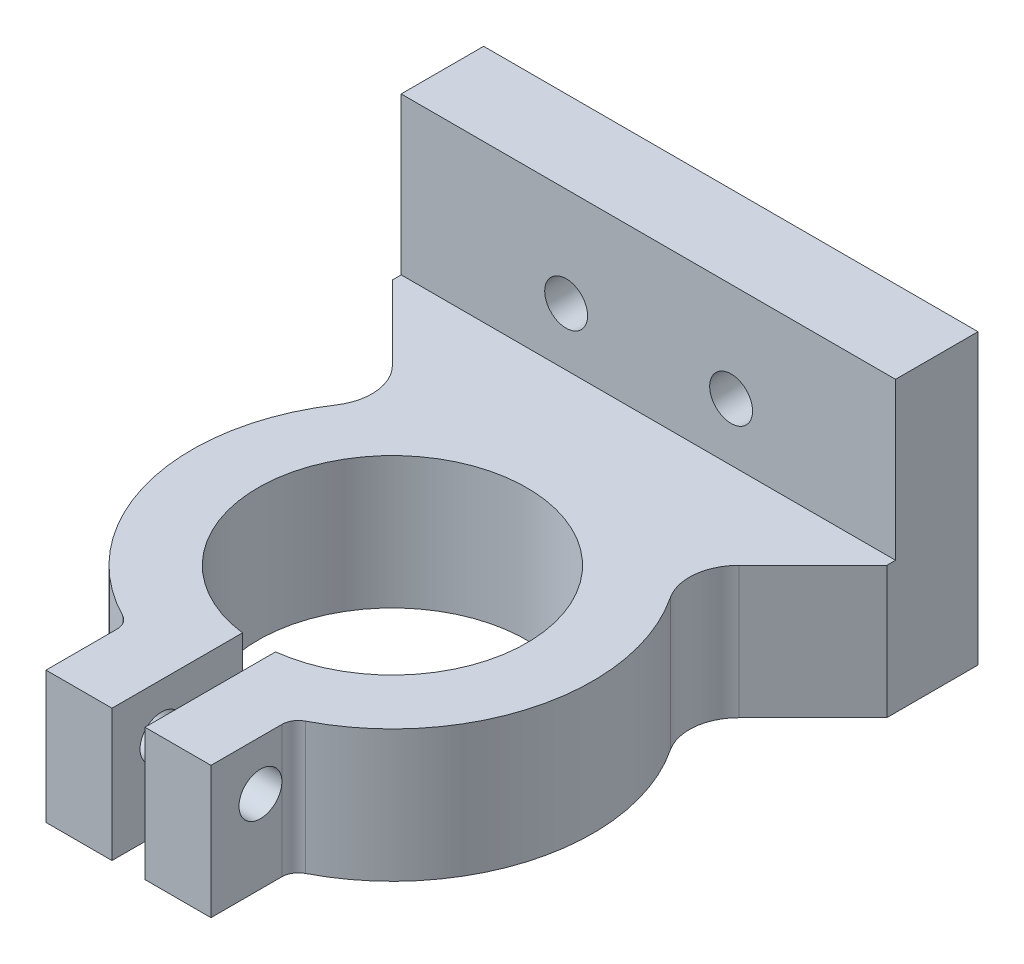
SolidWorks part; units mm, degrees
ref_plane "Front Plane" through (0, 0, 0) normal (0, 0, 1) x (1, 0, 0)
ref_plane "Top Plane" through (0, 0, 0) normal (0, 1, 0) x (1, 0, 0)
ref_plane "Right Plane" through (0, 0, 0) normal (1, 0, 0) x (0, 0, -1)
sketch "Sketch1" plane through (0, 0, 0) normal (0, 1, 0) x (1, 0, 0)
  line L0 (-28.2843, 0) -> (0, 28.2843) construction
  line L1 (-28.2843, 0) -> (0, -28.2843) construction
  line L2 (0, 28.2843) -> (28.2843, 0) construction
  line L3 (0, -28.2843) -> (28.2843, 0) construction
  line L4 (-28.2843, 0) -> (28.2843, 0) construction
  line L5 (0, 28.2843) -> (0, -28.2843) construction
  line L6 (-28.6378, -0.3536) -> (0, -28.9914)
  line L7 (0, -28.9914) -> (28.6378, -0.3536)
  point P1 (0, 0)
  dimension "D1" = 40
  dimension "D2" = 0.5
extrude "Extrude-Thin1" add sketch "Sketch1" along normal blind 60 thin contours L6 L7 thin type one direction wall 4
sketch "Sketch2" plane through (0, 0, 0) normal (0, 1, 0) x (1, 0, 0)
  line L0 (-31.4663, -3.182) -> (-31.4663, -85)
  line L1 (-31.4663, -85) -> (-2, -85)
  line L2 (31.4663, -85) -> (31.4663, -3.182)
  line L3 (-31.4663, -3.182) -> (0, -34.6482) construction
  line L4 (0, -34.6482) -> (31.4663, -3.182) construction
  line L5 (-31.4663, -3.182) -> (0, -34.6482)
  line L6 (0, -34.6482) -> (31.4663, -3.182)
  line L7 (0, -70) -> (0, -77.0884) construction
  line L8 (-2, -69.1768) -> (-2, -85)
  line L9 (0, -53) -> (0, -34.6482) construction
  line L11 (2, -69.1768) -> (2, -85)
  line L12 (-2, -69.1768) -> (2, -85) construction
  line L13 (-2, -85) -> (2, -69.1768) construction
  line L14 (2, -85) -> (31.4663, -85)
  arc A1 (2, -69.1768) -> (-2, -69.1768) centre (0, -53) ccw
  dimension "D4" = 16.3
  dimension "D1" = 85
  dimension "D2" = 4
  dimension "D3" = 32
extrude "Boss-Extrude1" add sketch "Sketch2" along normal blind 16
sketch "Sketch3" plane through (17.3241, 0, 17.3241) normal (0.7071, 0, 0.7071) x (0.7071, 0, -0.7071)
  line L0 (0, 50) -> (0, 20) construction
  line L1 (2.75, 50) -> (2.75, 20)
  line L2 (-2.75, 50) -> (-2.75, 20)
  arc A0 (2.75, 50) -> (-2.75, 50) centre (0, 50) ccw
  arc A1 (-2.75, 20) -> (2.75, 20) centre (0, 20) ccw
  point P3 (0, 35)
  dimension "D3" = 2.75
  dimension "D1" = 20
  dimension "D2" = 30
extrude "Cut-Extrude1" cut sketch "Sketch3" against normal through all
mirror "Mirror1" about plane through (0, 0, 0) normal (1, 0, 0) of "Cut-Extrude1"
sketch "Sketch5" plane through (0, 0, 0) normal (0, 1, 0) x (1, 0, 0)
  line L0 (-31.4663, -21.5337) -> (-17.1827, -35.8173)
  line L1 (-31.4663, -3.182) -> (-31.4663, -85) construction
  line L2 (-10, -75.147) -> (-10, -85)
  line L3 (-31.4663, -85) -> (-2, -85) construction
  line L4 (-31.4663, -3.182) -> (0, -34.6482) construction
  line L5 (-2, -85) -> (-2, -69.1768) construction
  line L6 (-10, -85) -> (-31.4663, -85)
  line L7 (-31.4663, -85) -> (-31.4663, -21.5337)
  arc A0 (-17.1827, -35.8173) -> (-10, -75.147) centre (0, -53) ccw
  arc A1 (2, -69.1768) -> (-2, -69.1768) centre (0, -53) ccw construction
  dimension "D1" = 8
  dimension "D2" = 8
extrude "Cut-Extrude2" cut sketch "Sketch5" along normal through all
mirror "Mirror2" about plane through (0, 0, 0) normal (1, 0, 0) of "Cut-Extrude2"
fillet "Fillet2" radius 2 2 edges at (10, 8, 75.147) (-10, 8, 75.147)
sketch "Sketch6" plane through (0, 0, 0) normal (1, 0, 0) x (0, 0, -1)
  line L0 (-85, 16) -> (-85, 0) construction
  circle A0 centre (-79, 10) radius 2.6
  dimension "D3" = 5.2
  dimension "D1" = 10
  dimension "D2" = 6
extrude "Cut-Extrude3" cut sketch "Sketch6" against normal through all both and the other way through all
sketch "Sketch7" plane through (-17.3241, 0, 17.3241) normal (-0.7071, 0, 0.7071) x (0.7071, 0, 0.7071)
  line L0 (24.5, 16) -> (-20, 16) construction
  line L1 (-40.1042, 68.8024) -> (38.3195, 68.8024)
  line L2 (-40.1042, 68.8024) -> (-40.1042, 16)
  line L3 (-40.1042, 16) -> (38.3195, 16)
  line L4 (38.3195, 68.8024) -> (38.3195, 16)
  dimension "D1" = 0
extrude "Cut-Extrude4" cut sketch "Sketch7" against normal through all and the other way through all
sketch "Sketch8" plane through (0, 16, 0) normal (0, 1, 0) x (1, 0, 0)
  line L1 (-25.3301, 9.3905) -> (25.9897, 9.3905)
  line L2 (-25.3301, 9.3905) -> (-25.3301, -30.6607)
  line L3 (-25.3301, -30.6607) -> (25.9897, -30.6607)
  line L4 (25.9897, 9.3905) -> (25.9897, -30.6607)
extrude "Boss-Extrude2" add sketch "Sketch8" against normal blind 16
sketch "Sketch9" plane through (0, 16, 0) normal (0, 1, 0) x (1, 0, 0)
  line L1 (-45.4357, 11.8389) -> (46.3414, 11.8389)
  line L2 (-45.4357, 11.8389) -> (-45.4357, -21.9738)
  line L3 (-45.4357, -21.9738) -> (46.3414, -21.9738)
  line L4 (46.3414, 11.8389) -> (46.3414, -21.9738)
extrude "Cut-Extrude5" cut sketch "Sketch9" against normal through all contours L2 L3 L4 L1
sketch "Sketch12" plane through (0, 0, 21.9738) normal (0, 0, -1) x (-1, 0, 0)
  line L1 (-31.4663, 35) -> (31.4663, 35)
  line L2 (-31.4663, 35) -> (-31.4663, 0)
  line L3 (-31.4663, 0) -> (31.4663, 0)
  line L4 (31.4663, 35) -> (31.4663, 0)
  line L5 (31.0262, 16) -> (-31.0262, 16) construction
  circle A0 centre (-10.0337, 23) radius 2.6
  circle A1 centre (9.9663, 23) radius 2.6
  dimension "D2" = 5.2
  dimension "D1" = 35
  dimension "D3" = 20
  dimension "D4" = 21.5
  dimension "D5" = 7
  dimension "D6" = 7
extrude "Boss-Extrude5" add sketch "Sketch12" along normal blind 10
sketch "Sketch13" plane through (0, 16, 0) normal (0, 1, 0) x (1, 0, 0)
  line L0 (-31.4663, -11.9738) -> (-31.4663, -21.9738) construction
  line L1 (-29.9663, 9.7462) -> (29.9663, 9.7462)
  line L2 (-29.9663, 9.7462) -> (-29.9663, -112.4878)
  line L3 (-29.9663, -112.4878) -> (29.9663, -112.4878)
  line L4 (29.9663, 9.7462) -> (29.9663, -112.4878)
  line L5 (-80.9085, 31.1558) -> (76.1784, 31.1558)
  line L6 (-80.9085, 31.1558) -> (-80.9085, -138.6275)
  line L7 (-80.9085, -138.6275) -> (76.1784, -138.6275)
  line L8 (76.1784, 31.1558) -> (76.1784, -138.6275)
  line L9 (31.4663, -11.9738) -> (31.4663, -21.9738) construction
  point P10 (31.4663, -16.9738)
  dimension "D1" = 1.5
  dimension "D2" = 1.5
extrude "Cut-Extrude6" cut sketch "Sketch13" against normal through all both and the other way through all
fillet "Fillet6" radius 6 2 edges at (-17.1827, 8, 35.8173) (17.1827, 8, 35.8173)
sketch "Sketch14" plane through (0, 0, 11.9738) normal (0, 0, -1) x (-1, 0, 0)
  line L0 (-29.9663, 0) -> (29.9663, 0) construction
  circle A0 centre (0, 10) radius 1.75
  dimension "D1" = 3.5
  dimension "D2" = 10
extrude "Cut-Extrude7" cut sketch "Sketch14" against normal blind 15
sketch "Sketch15" plane through (0, 16, 0) normal (0, 1, 0) x (1, 0, 0)
  line L0 (25.9897, -27.0103) -> (22.3393, -30.6607)
  line L1 (22.3393, -30.6607) -> (25.9897, -30.6607)
  line L2 (25.9897, -30.6607) -> (25.9897, -27.0103)
  line L3 (0, -66.1059) -> (0, -42.6171) construction
  line L4 (-25.9897, -30.6607) -> (-25.9897, -27.0103)
  line L5 (-22.3393, -30.6607) -> (-25.9897, -30.6607)
  line L6 (-25.9897, -27.0103) -> (-22.3393, -30.6607)
  point P12 (22.3393, -30.6607)
extrude "Cut-Extrude8" cut sketch "Sketch15" against normal blind 30
